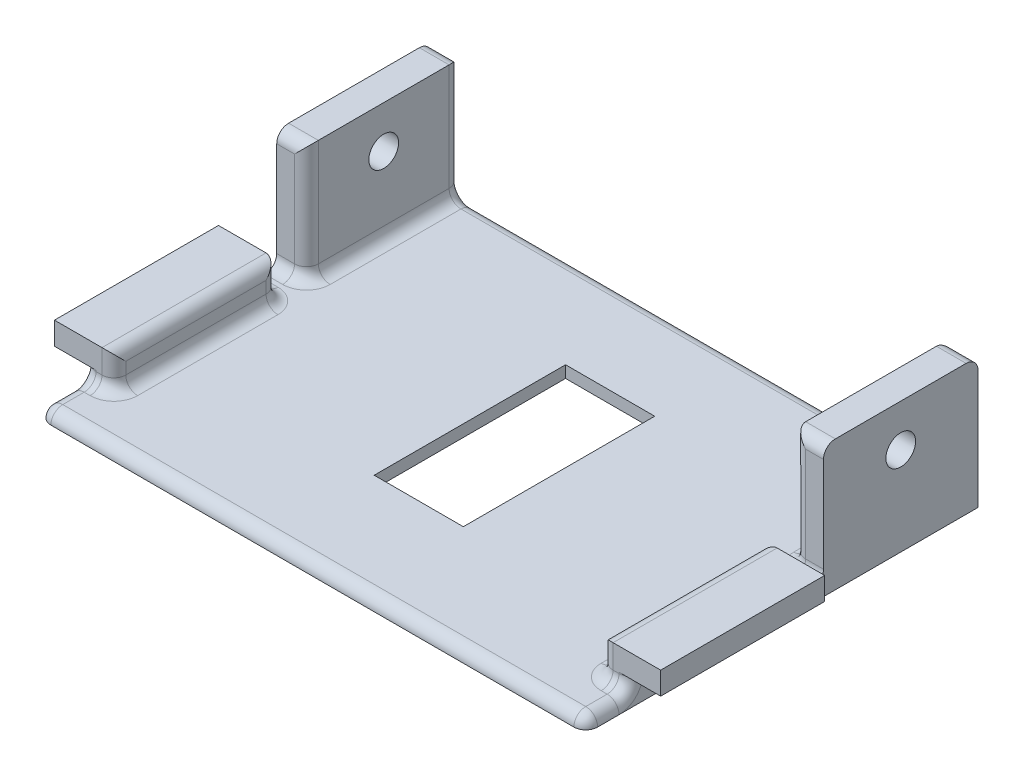
SolidWorks part; units mm, degrees
material "ABS"
ref_plane "Front" through (0, 0, 0) normal (0, 0, 1) x (1, 0, 0)
ref_plane "Top" through (0, 0, 0) normal (0, 1, 0) x (1, 0, 0)
ref_plane "Right" through (0, 0, 0) normal (1, 0, 0) x (0, 0, -1)
sketch "Sketch2" plane through (0, 0, 0) normal (0, 1, 0) x (1, 0, 0)
  line L1 (0, 0) -> (116.84, 0)
  line L2 (0, 0) -> (0, 33.02)
  line L3 (0, 33.02) -> (116.84, 33.02)
  line L4 (116.84, 0) -> (116.84, 33.02)
  dimension "D1" = 33.02
  dimension "D2" = 116.84
extrude "Boss-Extrude1" add sketch "Sketch2" along normal blind 2.54
sketch "Sketch3" plane through (0, 2.54, 0) normal (0, 1, 0) x (1, 0, 0)
  line L0 (0, 0) -> (116.84, 0) construction
  line L1 (0, 33.02) -> (6.35, 33.02)
  line L2 (0, 33.02) -> (0, 0)
  line L3 (0, 0) -> (6.35, 0)
  line L4 (6.35, 33.02) -> (6.35, 0)
  line L5 (116.84, 33.02) -> (0, 33.02) construction
  line L6 (110.49, 33.02) -> (116.84, 33.02)
  line L7 (110.49, 33.02) -> (110.49, 0)
  line L8 (110.49, 0) -> (116.84, 0)
  line L9 (116.84, 33.02) -> (116.84, 0)
  line L10 (116.84, 0) -> (116.84, 33.02) construction
  dimension "D1" = 6.35
  dimension "D2" = 6.35
extrude "Boss-Extrude2" add sketch "Sketch3" along normal blind 25.4
sketch "Sketch4" plane through (0, 0, 0) normal (-1, 0, 0) x (0, 0, 1)
  circle A0 centre (-16.51, 18.93) radius 3.175
  dimension "D1" = 6.35
extrude "Cut-Extrude1" cut sketch "Sketch4" against normal through all both and the other way through all
sketch "Sketch5" plane through (0, 0, 0) normal (0, 0, 1) x (1, 0, 0)
  line L0 (116.84, 27.94) -> (116.84, 0) construction
  line L1 (0, 0) -> (116.84, 0)
  line L2 (0, 0) -> (0, 2.54)
  line L3 (0, 2.54) -> (116.84, 2.54)
  line L4 (116.84, 0) -> (116.84, 2.54)
extrude "Boss-Extrude3" add sketch "Sketch5" along normal blind 50.8
sketch "Sketch6" plane through (0, 2.54, 0) normal (0, 1, 0) x (1, 0, 0)
  line L0 (0, -50.8) -> (0, 0) construction
  line L1 (0, -41.148) -> (6.35, -41.148)
  line L2 (0, -41.148) -> (0, -6.096)
  line L3 (0, -6.096) -> (6.35, -6.096)
  line L4 (6.35, -41.148) -> (6.35, -6.096)
  line L5 (116.84, -50.8) -> (116.84, 0) construction
  line L6 (116.84, -41.148) -> (110.49, -41.148)
  line L7 (116.84, -41.148) -> (116.84, -6.096)
  line L8 (116.84, -6.096) -> (110.49, -6.096)
  line L9 (110.49, -41.148) -> (110.49, -6.096)
  line L10 (116.84, -50.8) -> (0, -50.8) construction
  dimension "D1" = 9.652
  dimension "D2" = 9.652
  dimension "D3" = 35.052
  dimension "D4" = 35.052
  dimension "D5" = 6.35
  dimension "D6" = 6.35
extrude "Boss-Extrude4" add sketch "Sketch6" along normal blind 7.62
sketch "Sketch7" plane through (0, 0, 0) normal (-1, 0, 0) x (0, 0, 1)
  line L1 (6.096, 10.16) -> (41.148, 10.16)
  line L2 (6.096, 10.16) -> (6.096, 5.334)
  line L3 (6.096, 5.334) -> (41.148, 5.334)
  line L4 (41.148, 10.16) -> (41.148, 5.334)
  dimension "D1" = 5.334
extrude "Boss-Extrude5" add sketch "Sketch7" along normal blind 6.35
sketch "Sketch8" plane through (116.84, 0, 0) normal (1, 0, 0) x (0, 0, -1)
  line L1 (-6.096, 10.16) -> (-41.148, 10.16)
  line L2 (-6.096, 10.16) -> (-6.096, 5.334)
  line L3 (-6.096, 5.334) -> (-41.148, 5.334)
  line L4 (-41.148, 10.16) -> (-41.148, 5.334)
  dimension "D1" = 5.334
extrude "Boss-Extrude6" add sketch "Sketch8" along normal blind 6.35
fillet "Fillet1" radius 2.54 25 edges at (110.49, 15.24, -33.02) (58.42, 2.54, -33.02) (110.49, 10.16, 23.622) (6.35, 10.16, 23.622) (6.35, 15.24, -33.02) (6.35, 15.24, 0) (3.175, 2.54, 0) (6.35, 6.35, 6.096) (3.175, 2.54, 6.096) (6.35, 6.35, 41.148) (3.175, 2.54, 41.148) (110.49, 6.35, 41.148) (113.665, 2.54, 41.148) (110.49, 15.24, 0) (110.49, 6.35, 6.096) (113.665, 2.54, 6.096) (113.665, 2.54, 0) (110.49, 2.54, 23.622) (6.35, 2.54, 23.622) (110.49, 2.54, -16.51) (6.35, 2.54, -16.51) (113.665, 27.94, -33.02) (113.665, 27.94, 0) (3.175, 27.94, -33.02) (3.175, 27.94, 0)
sketch "Sketch11" plane through (0, 2.54, 0) normal (0, 1, 0) x (1, 0, 0)
  line L11 (44.0188, 1.4528) -> (46.6338, 1.4528)
  line L12 (46.6338, 1.4528) -> (46.6338, -21.664)
  line L13 (46.6338, -21.664) -> (44.0188, -21.664)
  line L14 (44.0188, -21.664) -> (44.0188, 1.4528)
  line L16 (18.287, 1.4528) -> (18.287, -21.664)
  line L17 (18.287, -21.664) -> (15.672, -21.664)
  line L18 (15.672, -21.664) -> (15.672, 1.4528)
  line L19 (15.672, 1.4528) -> (18.287, 1.4528)
  line L20 (18.287, 1.4528) -> (15.672, 1.4528)
  line L21 (15.672, -21.664) -> (18.287, -21.664)
  line L22 (44.0188, 1.4528) -> (46.6338, 1.4528)
  line L23 (46.6338, -21.664) -> (44.0188, -21.664)
  line L24 (15.672, 1.4528) -> (18.287, 1.4528)
sketch "Sketch14" plane through (0, 2.54, 0) normal (0, 1, 0) x (1, 0, 0)
  line L0 (58.42, 30.48) -> (58.42, -50.8)
  line L1 (107.95, 30.48) -> (8.89, 30.48) construction
  line L2 (116.84, -50.8) -> (0, -50.8) construction
ref_plane "Plane1" through (58.42, 0, 0) normal (1, 0, 0) x (0, 0, -1)
fillet "Fillet7" radius 2.54 2 edges at (116.84, 1.27, 50.8) (0, 1.27, 50.8)
fillet "Fillet8" radius 2.54 9 edges at (116.84, 5.207, 41.148) (116.84, 3.2839, 41.8919) (116.84, 2.54, 45.974) (116.0961, 2.54, 50.0561) (0, 5.207, 41.148) (0, 3.2839, 41.8919) (0, 2.54, 45.974) (0.7439, 2.54, 50.0561) (58.42, 2.54, 50.8)
sketch "Sketch16" plane through (0, 2.54, 0) normal (0, 1, 0) x (1, 0, 0)
  line L4 (48.895, 12.827) -> (67.945, 12.827)
  line L5 (67.945, 12.827) -> (67.945, -28.067)
  line L6 (67.945, -28.067) -> (48.895, -28.067)
  line L7 (48.895, -28.067) -> (48.895, 12.827)
extrude "Cut-Extrude2" cut sketch "Sketch16" against normal up to next
